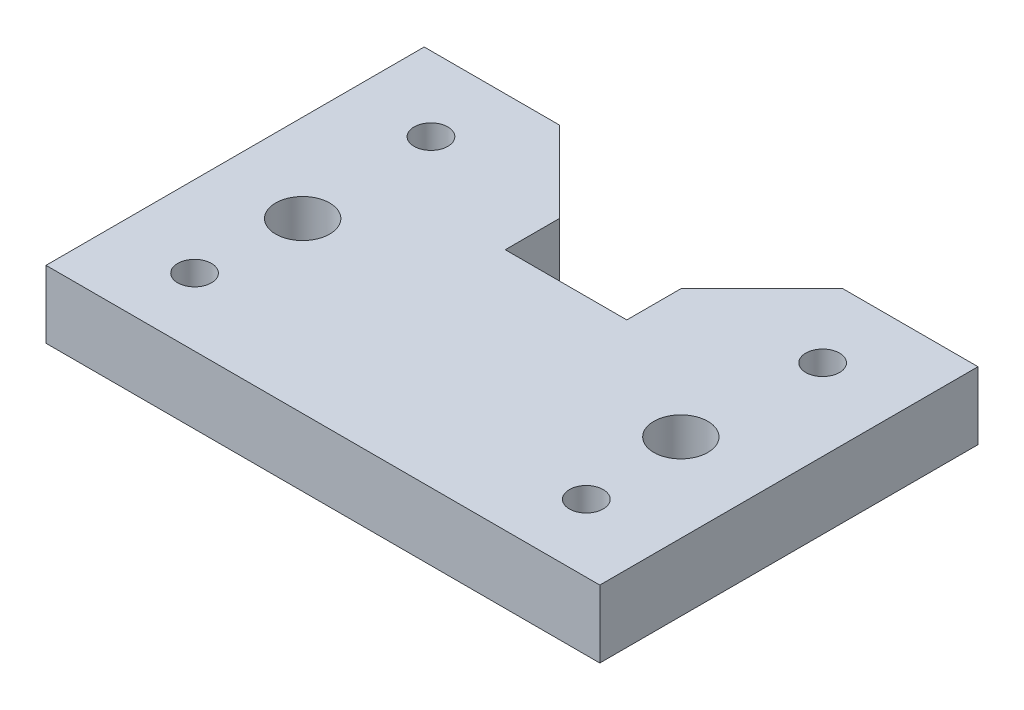
SolidWorks part; units mm, degrees
ref_plane "Front Plane" through (0, 0, 0) normal (0, 0, 1) x (1, 0, 0)
ref_plane "Top Plane" through (0, 0, 0) normal (0, 1, 0) x (1, 0, 0)
ref_plane "Right Plane" through (0, 0, 0) normal (1, 0, 0) x (0, 0, -1)
sketch "Sketch1" plane through (0, 0, 0) normal (0, 0, 1) x (1, 0, 0)
  line L0 (-41, 0) -> (41, 0)
  line L1 (-41, 0) -> (-41, -10)
  line L2 (-41, -10) -> (41, -10)
  line L3 (41, -10) -> (41, 0)
  line L4 (0, 0) -> (0, -10) construction
  dimension "D1" = 10
  dimension "D2" = 82
extrude "Boss-Extrude1" add sketch "Sketch1" along normal blind 35
sketch "Sketch2" plane through (0, 0, 0) normal (0, 1, 0) x (1, 0, 0)
  line L0 (41, -10) -> (-41, -10) construction
  line L3 (0, 0) -> (0, -35) construction
  line L4 (41, 0) -> (-41, 0) construction
  line L5 (41, -35) -> (-41, -35) construction
  line L6 (41, -35) -> (41, 0) construction
  line L7 (-41, -35) -> (-41, 0) construction
  circle A0 centre (-28, -10) radius 4
  circle A1 centre (28, -10) radius 4
  point P16 (0, 0)
  point P17 (0, 0)
  dimension "D1" = 56
  dimension "D2" = 8
  dimension "D3" = 10
extrude "Cut-Extrude1" cut sketch "Sketch2" against normal through all both and the other way through all
sketch "Sketch3" plane through (0, 0, 0) normal (0, 1, 0) x (1, 0, 0)
  line L0 (-41, -25) -> (41, -25) construction
  line L1 (-41, -35) -> (-41, 0) construction
  line L2 (41, -35) -> (41, 0) construction
  line L3 (41, -35) -> (-41, -35) construction
  line L4 (0, -35) -> (0, 0) construction
  circle A0 centre (-29, -25) radius 2.5
  circle A1 centre (29, -25) radius 2.5
  dimension "D2" = 5
  dimension "D3" = 58
  dimension "D1" = 10
extrude "Cut-Extrude2" cut sketch "Sketch3" against normal through all both and the other way through all
sketch "Sketch4" plane through (0, 0, 0) normal (0, 0, -1) x (-1, 0, 0)
  line L1 (41, -10) -> (-41, -10)
  line L2 (41, -10) -> (41, 0)
  line L3 (41, 0) -> (-41, 0)
  line L4 (-41, -10) -> (-41, 0)
extrude "Boss-Extrude2" add sketch "Sketch4" along normal blind 21
sketch "Sketch5" plane through (0, 0, 0) normal (0, 1, 0) x (1, 0, 0)
  line L0 (-41, 10) -> (41, 10) construction
  line L1 (-41, -35) -> (-41, 21) construction
  line L2 (41, -35) -> (41, 21) construction
  line L3 (0, 21) -> (0, -35) construction
  line L4 (-41, 21) -> (41, 21) construction
  line L5 (41, -35) -> (-41, -35) construction
  circle A0 centre (-29, 10) radius 2.5
  circle A1 centre (29, 10) radius 2.5
  dimension "D1" = 5
  dimension "D2" = 58
  dimension "D3" = 11
extrude "Cut-Extrude3" cut sketch "Sketch5" against normal through all both and the other way through all
sketch "Sketch6" plane through (0, -10, 0) normal (0, -1, 0) x (1, 0, 0)
  line L1 (-24.3812, 25) -> (-26.6906, 29)
  line L2 (-26.6906, 29) -> (-31.3094, 29)
  line L3 (-31.3094, 29) -> (-33.6188, 25)
  line L4 (-33.6188, 25) -> (-31.3094, 21)
  line L5 (-31.3094, 21) -> (-26.6906, 21)
  line L6 (-26.6906, 21) -> (-24.3812, 25)
  line L7 (33.6188, 25) -> (31.3094, 29)
  line L8 (31.3094, 29) -> (26.6906, 29)
  line L9 (26.6906, 29) -> (24.3812, 25)
  line L10 (24.3812, 25) -> (26.6906, 21)
  line L11 (26.6906, 21) -> (31.3094, 21)
  line L12 (31.3094, 21) -> (33.6188, 25)
  line L13 (-24.3812, -10) -> (-26.6906, -6)
  line L14 (-26.6906, -6) -> (-31.3094, -6)
  line L15 (-31.3094, -6) -> (-33.6188, -10)
  line L16 (-33.6188, -10) -> (-31.3094, -14)
  line L17 (-31.3094, -14) -> (-26.6906, -14)
  line L18 (-26.6906, -14) -> (-24.3812, -10)
  line L19 (33.6188, -10) -> (31.3094, -6)
  line L20 (31.3094, -6) -> (26.6906, -6)
  line L21 (26.6906, -6) -> (24.3812, -10)
  line L22 (24.3812, -10) -> (26.6906, -14)
  line L23 (26.6906, -14) -> (31.3094, -14)
  line L24 (31.3094, -14) -> (33.6188, -10)
  circle A0 centre (-29, 25) radius 4 construction
  circle A1 centre (29, 25) radius 4 construction
  circle A2 centre (-29, -10) radius 4 construction
  circle A3 centre (29, -10) radius 4 construction
  point P28 (-29, 21)
  dimension "D1" = 8
  dimension "D2" = 8
  dimension "D3" = 8
  dimension "D4" = 8
extrude "Cut-Extrude4" cut sketch "Sketch6" against normal blind 4
sketch "Sketch7" plane through (0, 0, 0) normal (0, 1, 0) x (1, 0, 0)
  line L1 (-41, 21) -> (41, 21) construction
  line L2 (0, 1) -> (0, 21) construction
  line L4 (21, 21) -> (-21, 21)
  line L5 (9, 9) -> (9, 1)
  line L6 (-9, 9) -> (-9, 1)
  line L8 (-9, 1) -> (9, 1)
  line L9 (-9, 9) -> (-21, 21)
  line L10 (9, 9) -> (21, 21)
  point P0 (-9, 9)
  dimension "D1" = 42
  dimension "D2" = 18
  dimension "D3" = 20
extrude "Cut-Extrude5" cut sketch "Sketch7" against normal through all both and the other way through all
